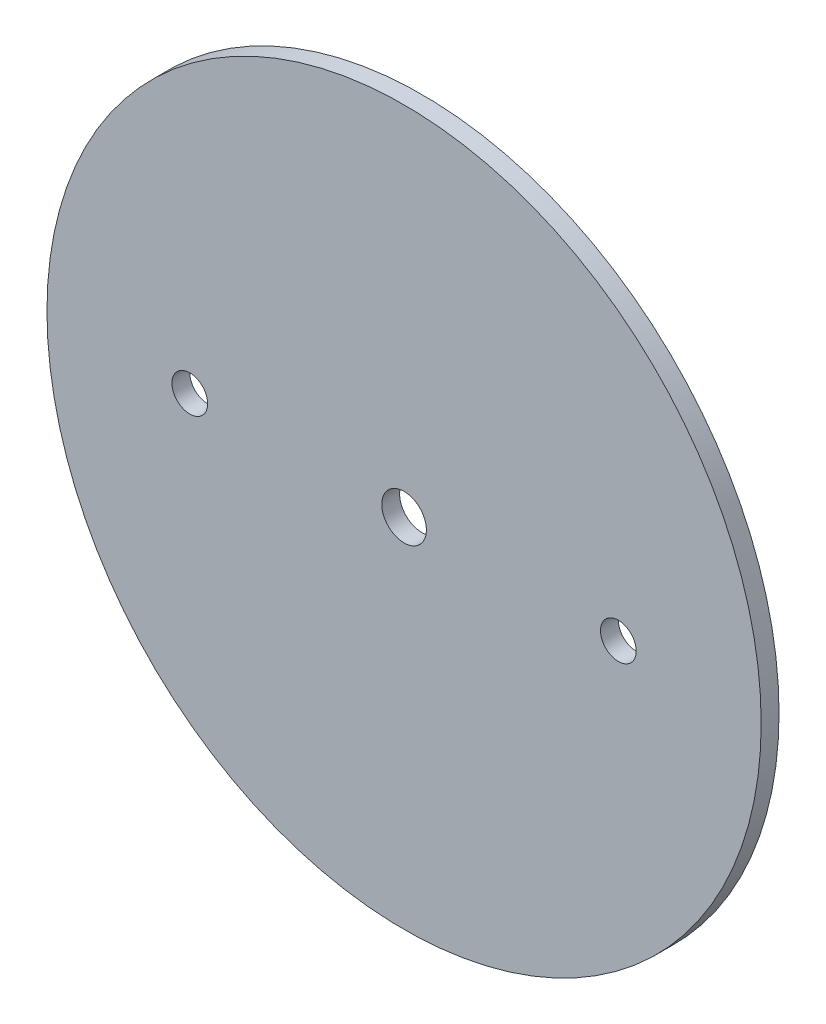
SolidWorks part; units mm, degrees
ref_plane "Front Plane" through (0, 0, 0) normal (0, 0, 1) x (1, 0, 0)
ref_plane "Top Plane" through (0, 0, 0) normal (0, 1, 0) x (1, 0, 0)
ref_plane "Right Plane" through (0, 0, 0) normal (1, 0, 0) x (0, 0, -1)
sketch "Sketch1" plane through (0, 0, 0) normal (0, 0, 1) x (1, 0, 0)
  circle A0 centre (0, 0) radius 63.5
  dimension "D1" = 127
extrude "Boss-Extrude1" add sketch "Sketch1" along normal mid plane 3.175
sketch "Sketch2" plane through (0, 0, 1.5875) normal (0, 0, 1) x (1, 0, 0)
  line L0 (-1000, 0) -> (49000, 0) construction
  line L1 (0, -1000) -> (0, 49000) construction
  point P4 (38.1, 0)
  point P5 (-38.1, 0)
  dimension "D2" = 76.2
  dimension "D1" = 38.1
hole_wizard "1/4 (0.25) Diameter Hole1" positions "Sketch2" profile "Sketch3" hole size "1/4" standard "ANSI Inch" end condition through all
sketch "Sketch3" plane through (-38.1, 0, 1.5875) normal (1, 0, 0) x (0, -1, 0)
  line L0 (0, 0) -> (0, 3.175)
  line L1 (0, 3.175) -> (3.175, 3.175)
  line L2 (3.175, 3.175) -> (3.175, 0)
  line L5 (3.175, 0) -> (0, 0)
  line L11 (0, -6.35) -> (0, 107.95) construction
  dimension "Thru Hole Dia." = 6.35
  dimension "Thru Hole Depth" = 3.175
sketch "Sketch4" plane through (0, 0, 1.5875) normal (0, 0, 1) x (1, 0, 0)
  point P0 (0, 0)
hole_wizard "5/16 (0.3125) Diameter Hole1" positions "Sketch4" profile "Sketch5" hole size "5/16" standard "ANSI Inch"
sketch "Sketch5" plane through (0, 0, 1.5875) normal (1, 0, 0) x (0, -1, 0)
  line L0 (0, 0) -> (0, 3.302)
  line L1 (0, 3.302) -> (3.9687, 3.302)
  line L2 (3.9687, 3.302) -> (3.9688, 0)
  line L5 (3.9688, 0) -> (0, 0)
  line L10 (0, 3.302) -> (-3.9688, 3.302) construction
  line L11 (0, -6.35) -> (0, 107.95) construction
  dimension "Hole Dia." = 7.9375
  dimension "Hole Depth" = 3.302
  dimension "Drill Angle" = 180
equation "\"AIRFRAME_OD\"= 5.15in"
equation "\"AIRFRAME_ID\"= 5.00in"
equation "\"FLAT_T\"= 0.125in"
equation "\"NOSE_EXP_L\"= 27in"
equation "\"NOSE_SHOULDER_L\"= 5in"
equation "\"MAIN_L\"= 30in"
equation "\"RECO_COUP_L\"= 10in"
equation "\"RECO_SWITCH_L\"= 2in"
equation "\"DROGUE_L\"= 20in"
equation "\"ATS_FORE_COUP_L\"= 5.5in"
equation "\"ATS_AFT_COUP_L\"= 4.5in"
equation "\"LOWER_L\"= 30in"
equation "\"FIN_N\"= 4"
equation "\"CR_AFT_X\"= 0.5in"
equation "\"CR_FORE_X\"= 9.25in"
equation "\"FIN_ROOT\"= 8in"
equation "\"FIN_X\"= 0.75in"
equation "\"MOTOR_OD\"= 3.091in"
equation "\"MOTOR_ID\"= 3.00in"
equation "\"COUPLER_OD\"= 4.998in"
equation "\"COUPLER_ID\"= 4.88in"
equation "\"D1@Sketch1\"=\"AIRFRAME_ID\""
equation "\"D1@Boss-Extrude1\"=\"FLAT_T\""
equation "\"RECO_ROD_X\"= 3.5in"
equation "\"ATS_ROD_X\"= 3in"
equation "\"D2@Sketch2\"=\"ATS_ROD_X\""
equation "\"MOTOR_L\"= 14in"
equation "\"MOTOR_LOWER_X\"= 2in"
equation "\"D1@Sketch2\"=\"ATS_ROD_X\"/2"
